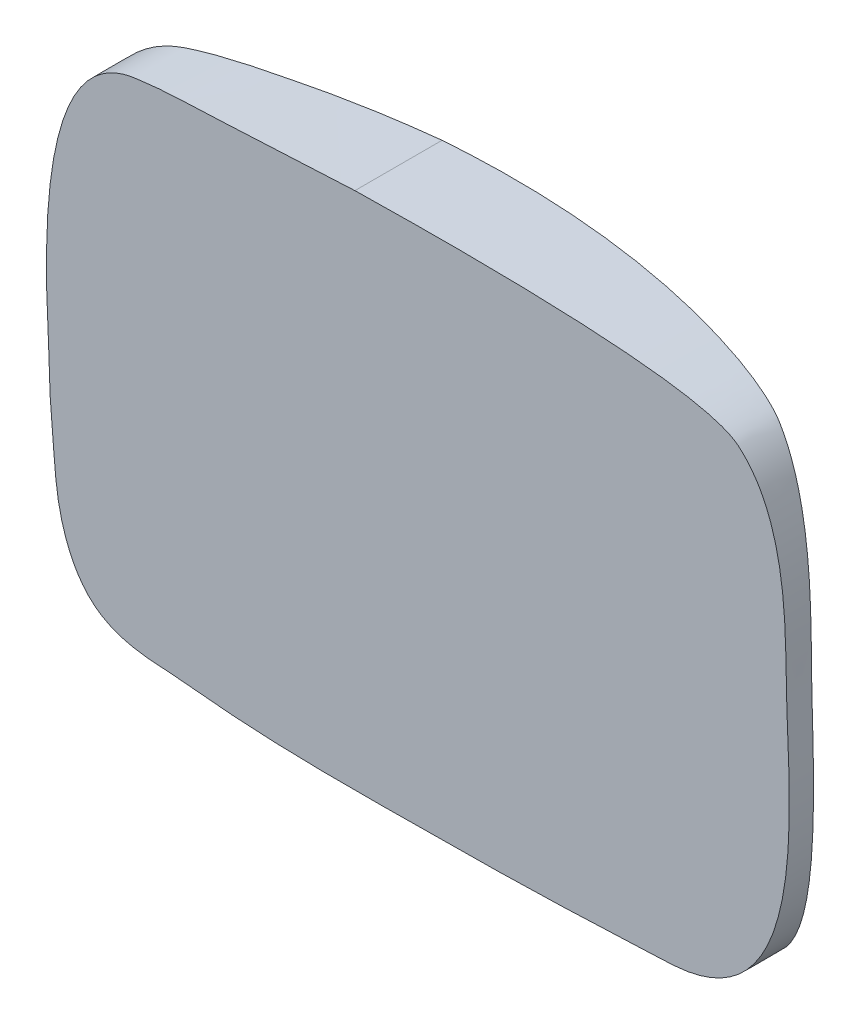
SolidWorks part; units mm, degrees
ref_plane "정면" through (0, 0, 0) normal (0, 0, 1) x (1, 0, 0)
ref_plane "윗면" through (0, 0, 0) normal (0, 1, 0) x (1, 0, 0)
ref_plane "우측면" through (0, 0, 0) normal (1, 0, 0) x (0, 0, -1)
sketch "스케치1" plane through (0, 0, 0) normal (0, 0, 1) x (1, 0, 0)
  line L0 (4.3782, 109.4709) -> (204.3782, 109.4709) construction
  spline S0 degree 3 poles (-29.2884, -13.1957) (-31.9398, -11.0264) (-33.0083, -6.7973) (-33.2884, -3.5291) (-33.5643, -0.311) (-33.9152, 2.908) (-33.9551, 6.1376) (-34.0153, 11.0124) (-36.4982, 34.3676) (-25.2884, 36.1376) (-22.0981, 36.6413) (-18.8462, 36.6173) (-15.6218, 36.8043) (-11.1792, 37.0618) (-6.7329, 37.2487) (-2.2884, 37.4709) knots 6 6 6 6 7 7 7 8 8 8 9 9 9 10 10 10 11 11 11 11
  spline S1 degree 3 poles (-2.2884, 37.4709) (-0.7664, 37.4492) (32.572, 38.4761) (37.3782, 34.4709) (42.3023, 30.3676) (42.3087, 21.3004) (42.3782, 15.8043) (42.4989, 6.2737) (45.558, -14.8494) (30.3782, -15.5291) (23.6036, -15.8324) (16.8262, -16.1499) (10.0449, -16.1957) (0.2648, -16.2618) (-9.568, -16.6091) (-19.2884, -15.5291) (-22.6891, -15.1512) (-26.4426, -15.5241) (-29.2884, -13.1957) knots 0 0 0 0 1 1 1 2 2 2 3 3 3 4 4 4 5 5 5 6 6 6 6
extrude "보스-돌출1" add sketch "스케치1" along normal blind 10 contours S1 S0
sketch "스케치3" plane through (0, 0, 0) normal (0, 1, 0) x (1, 0, 0)
  line L0 (-34.2295, 0) -> (42.7085, 0)
  line L1 (-34.2295, 0) -> (-34.2295, -7.5)
  line L2 (42.7085, 0) -> (42.7085, -7.5)
  arc A0 (-34.2295, -7.5) -> (42.7085, -7.5) centre (4.2395, -114.3106) cw
  point P0 (-34.2295, 0)
  point P1 (42.7085, 0)
  point P7 (4.2395, -0.7836)
  dimension "D2" = 76.938
  dimension "D1" = 7.5
  dimension "D3" = 38.469
extrude "컷-돌출2" cut sketch "스케치3" against normal mid plane 100
sketch "스케치4" plane through (0, 0, 0) normal (0, 0, 1) x (1, 0, 0)
  line L0 (11.0005, 22.6832) -> (11.0005, -1.3168)
  line L1 (11.0005, -1.3168) -> (-9.7841, 10.6832)
  line L2 (-9.7841, 10.6832) -> (11.0005, 22.6832)
  dimension "D1" = 24
  dimension "D2" = 24
  dimension "D3" = 24
  dimension "D4" = 20.7846
extrude "컷-돌출3" cut sketch "스케치4" along normal blind 2
